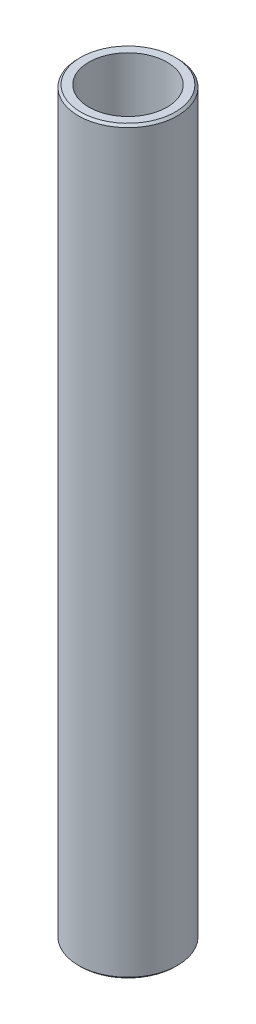
SolidWorks part; units mm, degrees
ref_plane "Front Plane" through (0, 0, 0) normal (0, 0, 1) x (1, 0, 0)
ref_plane "Top Plane" through (0, 0, 0) normal (0, 1, 0) x (1, 0, 0)
ref_plane "Right Plane" through (0, 0, 0) normal (1, 0, 0) x (0, 0, -1)
sketch "Sketch1" plane through (0, 0, 0) normal (0, 1, 0) x (1, 0, 0)
  circle A0 centre (0, 0) radius 17.5
  dimension "SHAFT_OD" = 35
extrude "Boss-Extrude1" add sketch "Sketch1" along normal blind 261.3493
sketch "Sketch2" plane through (0, 0, 0) normal (0, 1, 0) x (1, 0, 0)
  circle A0 centre (0, 0) radius 13.7969
  dimension "BORE_D" = 27.5937
extrude "Cut-Extrude1" cut sketch "Sketch2" along normal through all
chamfer "Chamfer1" distance 0.7857 angle 45 2 edges at (0, 261.3493, 17.5) (0, 0, 17.5)
